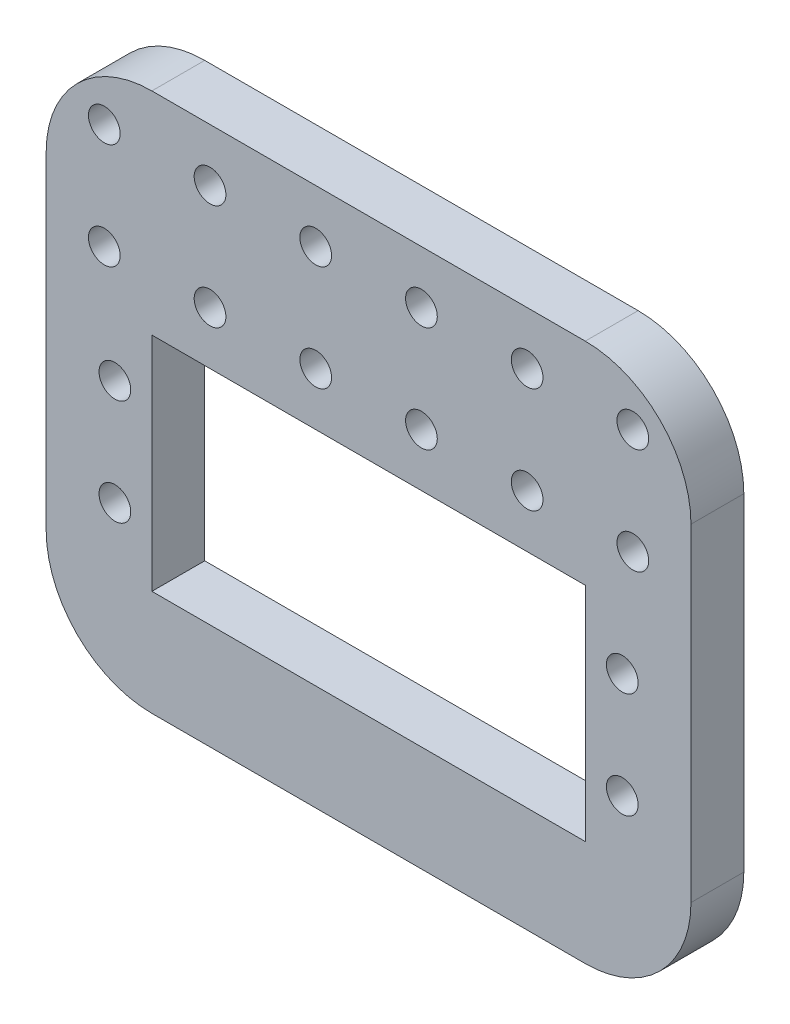
SolidWorks part; units mm, degrees
ref_plane "Plan de face" through (0, 0, 0) normal (0, 0, 1) x (1, 0, 0)
ref_plane "Plan de dessus" through (0, 0, 0) normal (0, 1, 0) x (1, 0, 0)
ref_plane "Plan de droite" through (0, 0, 0) normal (1, 0, 0) x (0, 0, -1)
sketch "Esquisse1" plane through (0, 0, 0) normal (0, 0, 1) x (1, 0, 0)
  line L8 (13.2541, 31.1988) -> (13.2541, -9.8012)
  line L9 (13.2541, -9.8012) -> (54.2541, -9.8012)
  line L10 (54.2541, -9.8012) -> (54.2541, 31.1988)
  line L11 (13.2541, 31.1988) -> (3.2541, 31.1988)
  line L12 (3.2541, 31.1988) -> (3.2541, -19.8012)
  line L13 (3.2541, -19.8012) -> (64.2541, -19.8012)
  line L14 (64.2541, -19.8012) -> (64.2541, 31.1988)
  line L15 (64.2541, 31.1988) -> (54.2541, 31.1988)
  line L17 (54.2541, 11.1988) -> (13.2541, 11.1988)
  line L18 (54.2541, 11.1988) -> (54.2541, 31.1988)
  line L19 (54.2541, 31.1988) -> (13.2541, 31.1988)
  line L20 (13.2541, 11.1988) -> (13.2541, 31.1988)
  dimension "D1" = 41
  dimension "D2" = 41
  dimension "D3" = 41
  dimension "D4" = 10
  dimension "D5" = 10
  dimension "D6" = 10
  dimension "D7" = 21
  dimension "D8" = 20
extrude "Boss.-Extru.3" add sketch "Esquisse1" along normal blind 5 contours L10 L19 L8 L17 | L14 L15 L10 L9 L8 L11 L12 L13 region at (33.7541, 21.1988, 0) region at (12.4589, 21.1988, 0)
sketch "Esquisse3" plane through (0, 0, 5) normal (0, 0, 1) x (1, 0, 0)
  line L0 (54.2541, -9.8012) -> (54.2541, 11.1988) construction
  line L1 (13.2541, 11.1988) -> (13.2541, -9.8012) construction
  line L2 (13.2541, -9.8012) -> (54.2541, -9.8012) construction
  circle A0 centre (9.7541, -4.3012) radius 1.5
  circle A1 centre (9.7541, 5.6988) radius 1.5
  circle A2 centre (57.7541, 5.6988) radius 1.5
  circle A3 centre (57.7541, -4.3012) radius 1.5
  dimension "D3" = 3
  dimension "D4" = 3
  dimension "D5" = 3.5
  dimension "D6" = 3.5
  dimension "D7" = 5.5
  dimension "D8" = 5.5
  dimension "D1" = 10
  dimension "D2" = 10
extrude "Enlèv. mat.-Extru.2" cut sketch "Esquisse3" against normal blind 5
sketch "Esquisse4" plane through (0, 0, 5) normal (0, 0, 1) x (1, 0, 0)
  line L0 (3.2541, 31.1988) -> (3.2541, -19.8012) construction
  line L1 (64.2541, 31.1988) -> (3.2541, 31.1988) construction
  circle A0 centre (8.7541, 26.1988) radius 1.5
  circle A1 centre (18.7541, 26.1988) radius 1.5
  circle A2 centre (28.7541, 26.1988) radius 1.5
  circle A3 centre (38.7541, 26.1988) radius 1.5
  circle A4 centre (48.7541, 26.1988) radius 1.5
  circle A5 centre (58.7541, 26.1988) radius 1.5
  circle A6 centre (18.7541, 16.1988) radius 1.5
  circle A7 centre (28.7541, 16.1988) radius 1.5
  circle A8 centre (38.7541, 16.1988) radius 1.5
  circle A9 centre (48.7541, 16.1988) radius 1.5
  circle A10 centre (58.7541, 16.1988) radius 1.5
  circle A11 centre (8.7541, 16.1988) radius 1.5
  dimension "D1" = 3
  dimension "D2" = 5.5
  dimension "D3" = 5
  dimension "D4" = 6
  dimension "D5" = 2
extrude "Enlèv. mat.-Extru.3" cut sketch "Esquisse4" against normal blind 5
fillet "Congé1" radius 10 4 edges at (3.2541, 31.1988, 2.5) (64.2541, 31.1988, 2.5) (3.2541, -19.8012, 2.5) (64.2541, -19.8012, 2.5)
